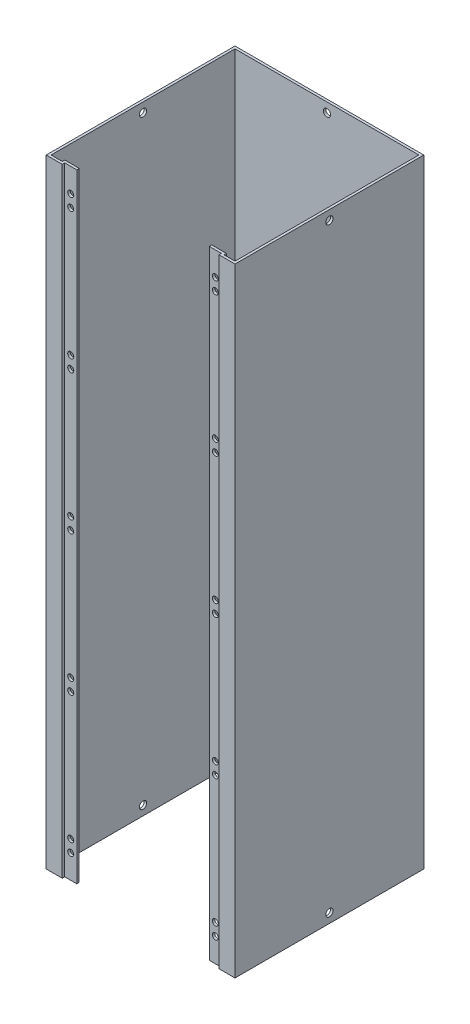
SolidWorks part; units mm, degrees
ref_plane "Front Plane" through (0, 0, 0) normal (0, 0, 1) x (1, 0, 0)
ref_plane "Top Plane" through (0, 0, 0) normal (0, 1, 0) x (1, 0, 0)
ref_plane "Right Plane" through (0, 0, 0) normal (1, 0, 0) x (0, 0, -1)
sketch "Sketch1" plane through (0, 0, 0) normal (0, 1, 0) x (1, 0, 0)
  line L0 (0, 0) -> (0, 100)
  line L1 (0, 100) -> (100, 100)
  line L2 (100, 100) -> (100, 0)
  line L3 (100, 0) -> (91.5, 0)
  line L4 (91.5, 0) -> (91.5, 1.3)
  line L5 (91.5, 1.3) -> (85.1, 1.3)
  line L6 (85.1, 1.3) -> (85.1, 2.6)
  line L7 (85.1, 2.6) -> (92.8, 2.6)
  line L8 (92.8, 2.6) -> (92.8, 1.3)
  line L9 (92.8, 1.3) -> (98.7, 1.3)
  line L10 (98.7, 1.3) -> (98.7, 98.7)
  line L11 (98.7, 98.7) -> (1.3, 98.7)
  line L12 (1.3, 98.7) -> (1.3, 1.3)
  line L13 (1.3, 1.3) -> (7.2, 1.3)
  line L14 (7.2, 1.3) -> (7.2, 2.6)
  line L15 (7.2, 2.6) -> (14.9, 2.6)
  line L16 (14.9, 2.6) -> (14.9, 1.3)
  line L17 (14.9, 1.3) -> (8.5, 1.3)
  line L18 (8.5, 1.3) -> (8.5, 0)
  line L19 (8.5, 0) -> (0, 0)
  dimension "D1" = 8.5
  dimension "D2" = 8.5
  dimension "D3" = 100
  dimension "D4" = 100
  dimension "D5" = 1.3
  dimension "D6" = 1.3
  dimension "D7" = 1.3
  dimension "D8" = 1.3
  dimension "D9" = 1.3
  dimension "D10" = 1.3
  dimension "D11" = 1.3
  dimension "D12" = 1.3
  dimension "D13" = 1.3
  dimension "D14" = 14.9
  dimension "D15" = 14.9
  dimension "D16" = 0
  dimension "D17" = 0
extrude "Boss-Extrude1" add sketch "Sketch1" along normal blind 327.5
sketch "Sketch2" plane through (0, 0, -1.3) normal (0, 0, 1) x (1, 0, 0)
  line L0 (8.5, 327.5) -> (14.9, 327.5) construction
  line L1 (14.9, 327.5) -> (14.9, 0) construction
  line L2 (85.1, 327.5) -> (85.1, 0) construction
  line L3 (85.1, 327.5) -> (91.5, 327.5) construction
  line L4 (8.5, 0) -> (14.9, 0) construction
  circle A0 centre (11.7, 314.9) radius 1.6
  circle A1 centre (11.7, 308.5) radius 1.6
  circle A2 centre (88.3, 314.9) radius 1.6
  circle A3 centre (88.3, 308.5) radius 1.6
  circle A4 centre (11.7, 240.925) radius 1.6
  circle A5 centre (11.7, 234.525) radius 1.6
  circle A6 centre (88.3, 240.925) radius 1.6
  circle A7 centre (88.3, 234.525) radius 1.6
  circle A8 centre (11.7, 166.95) radius 1.6
  circle A9 centre (11.7, 160.55) radius 1.6
  circle A10 centre (88.3, 166.95) radius 1.6
  circle A11 centre (88.3, 160.55) radius 1.6
  circle A12 centre (11.7, 92.975) radius 1.6
  circle A13 centre (11.7, 86.575) radius 1.6
  circle A14 centre (88.3, 92.975) radius 1.6
  circle A15 centre (88.3, 86.575) radius 1.6
  circle A16 centre (11.7, 19) radius 1.6
  circle A17 centre (11.7, 12.6) radius 1.6
  circle A18 centre (88.3, 19) radius 1.6
  circle A19 centre (88.3, 12.6) radius 1.6
  dimension "D1" = 3.2
  dimension "D2" = 3.2
  dimension "D3" = 12.6
  dimension "D4" = 6.4
  dimension "D5" = 3.2
  dimension "D6" = 3.2
  dimension "D8" = 3.2
  dimension "D9" = 3.2
  dimension "D10" = 12.6
  dimension "D12" = 12.6
  dimension "D7" = 2
  dimension "D11" = 5
extrude "Cut-Extrude2" cut sketch "Sketch2" against normal blind 10
sketch "Sketch3" plane through (100, 0, 0) normal (1, 0, 0) x (0, 0, -1)
  line L0 (0, 327.5) -> (100, 327.5) construction
  line L1 (0, 327.5) -> (0, 0) construction
  line L2 (100, 327.5) -> (100, 0) construction
  line L3 (0, 0) -> (100, 0) construction
  circle A0 centre (50, 322.524) radius 1.93
  circle A1 centre (50, 4.976) radius 1.93
  point P8 (101.7856, 281.8399)
  dimension "D1" = 3.86
  dimension "D7" = 3.86
  dimension "D2" = 4.976
  dimension "D3" = 50
  dimension "D4" = 50
  dimension "D5" = 50
  dimension "D6" = 4.976
extrude "Cut-Extrude3" cut sketch "Sketch3" against normal blind 100
sketch "Sketch4" plane through (0, 0, -100) normal (0, 0, -1) x (-1, 0, 0)
  line L0 (-100, 327.5) -> (0, 327.5) construction
  line L1 (0, 327.5) -> (0, 0) construction
  line L2 (-100, 0) -> (0, 0) construction
  circle A0 centre (-50, 322.524) radius 1.93
  circle A1 centre (-50, 4.976) radius 1.93
  dimension "D1" = 3.86
  dimension "D2" = 3.86
  dimension "D3" = 4.976
  dimension "D4" = 50
  dimension "D5" = 4.976
  dimension "D6" = 50
extrude "Cut-Extrude4" cut sketch "Sketch4" against normal blind 10
